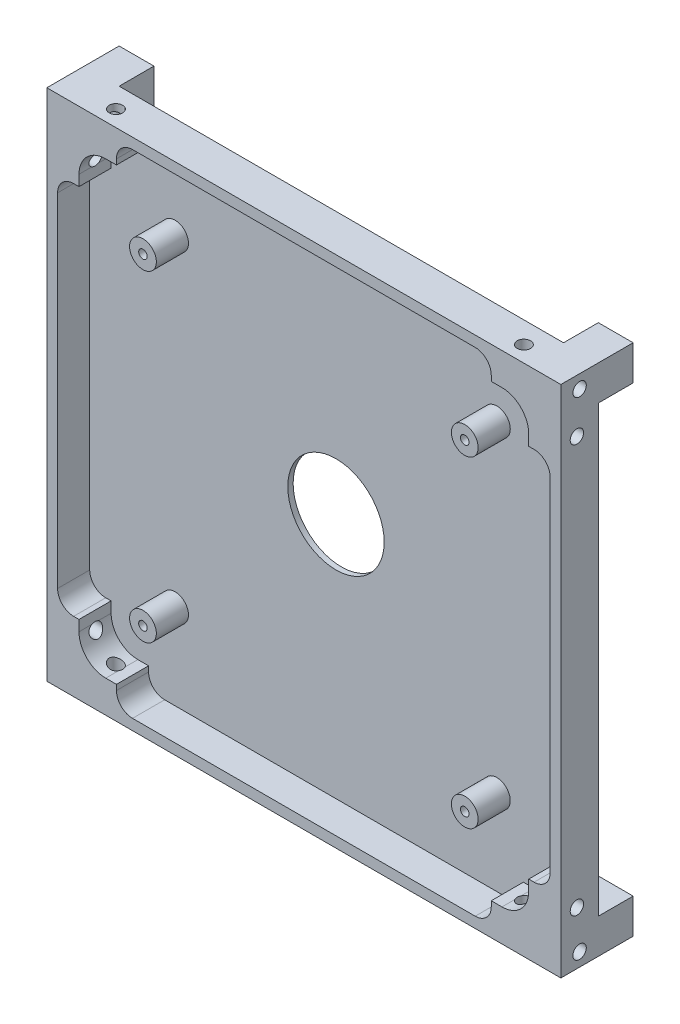
SolidWorks part; units mm, degrees
material "7075-T6 (SN)"
ref_plane "Front Plane" through (0, 0, 0) normal (0, 0, 1) x (1, 0, 0)
ref_plane "Top Plane" through (0, 0, 0) normal (0, 1, 0) x (1, 0, 0)
ref_plane "Right Plane" through (0, 0, 0) normal (1, 0, 0) x (0, 0, -1)
sketch "Sketch1" plane through (0, 0, 0) normal (0, 0, 1) x (1, 0, 0)
  line L1 (48, -48) -> (-48, -48)
  line L2 (48, -48) -> (48, 48)
  line L3 (48, 48) -> (-48, 48)
  line L4 (-48, -48) -> (-48, 48)
  line L5 (48, -48) -> (-48, 48) construction
  line L6 (48, 48) -> (-48, -48) construction
  point P0 (0, 0)
  dimension "D1" = 96
  dimension "D2" = 96
extrude "Boss-Extrude1" add sketch "Sketch1" along normal blind 2
sketch "Sketch2" plane through (0, 0, 2) normal (0, 0, 1) x (1, 0, 0)
  line L0 (48, 48) -> (-48, 48) construction
  line L1 (37, -42) -> (-37, -42)
  line L2 (42, -37) -> (42, 37)
  line L3 (37, 42) -> (-37, 42)
  line L4 (-42, -37) -> (-42, 37)
  line L5 (42, -42) -> (-42, 42) construction
  line L6 (42, 42) -> (-42, -42) construction
  line L7 (48, -48) -> (48, 48) construction
  line L12 (-48, 48) -> (-48, -48)
  line L13 (-48, -48) -> (48, -48)
  line L14 (48, -48) -> (48, 48)
  line L15 (48, 48) -> (-48, 48)
  line L16 (-48, 48) -> (-48, -48)
  line L17 (-48, -48) -> (48, -48)
  line L18 (48, -48) -> (48, 48)
  line L19 (48, 48) -> (-48, 48)
  arc A0 (-37, -42) -> (-42, -37) centre (-37, -37) cw
  arc A1 (37, -42) -> (42, -37) centre (37, -37) ccw
  arc A2 (42, 37) -> (37, 42) centre (37, 37) ccw
  arc A3 (-37, 42) -> (-42, 37) centre (-37, 37) ccw
  point P0 (0, 0)
  dimension "D4" = 5
  dimension "D1" = 6
  dimension "D2" = 6
extrude "Boss-Extrude2" add sketch "Sketch2" along normal blind 5
sketch "Sketch4" plane through (0, 0, 7) normal (0, 0, 1) x (1, 0, 0)
  line L0 (-41.5, 41.5) -> (41.5, -41.5) construction
  line L1 (-41.5, 41.5) -> (41.5, 41.5)
  line L2 (-41.5, 41.5) -> (-41.5, -41.5)
  line L3 (-41.5, -41.5) -> (41.5, -41.5)
  line L4 (41.5, 41.5) -> (41.5, -41.5)
  point P4 (0, 0)
  dimension "D1" = 83
  dimension "D2" = 83
sketch "Sketch3" plane through (0, 0, 0) normal (0, 0, -1) x (-1, 0, 0)
  line L1 (-48, 48) -> (-41.5, 48)
  line L2 (-48, 48) -> (-48, 41.5)
  line L3 (-48, 41.5) -> (-41.5, 41.5)
  line L4 (-41.5, 48) -> (-41.5, 41.5)
  line L5 (48, 48) -> (41.5, 48)
  line L6 (48, 48) -> (48, 41.5)
  line L7 (48, 41.5) -> (41.5, 41.5)
  line L8 (41.5, 48) -> (41.5, 41.5)
  line L9 (-48, -48) -> (-41.5, -48)
  line L10 (-48, -48) -> (-48, -41.5)
  line L11 (-48, -41.5) -> (-41.5, -41.5)
  line L12 (-41.5, -48) -> (-41.5, -41.5)
  line L13 (48, -48) -> (41.5, -48)
  line L14 (48, -48) -> (48, -41.5)
  line L15 (48, -41.5) -> (41.5, -41.5)
  line L16 (41.5, -48) -> (41.5, -41.5)
  dimension "D1" = 6.5
  dimension "D2" = 6.5
  dimension "D3" = 6.5
  dimension "D4" = 6.5
extrude "Boss-Extrude3" add sketch "Sketch3" along normal blind 6.5
sketch "Sketch5" plane through (0, 0, 0) normal (0, 0, -1) x (-1, 0, 0)
  circle A0 centre (0, 0) radius 9
  dimension "D1" = 18
extrude "Cut-Extrude1" cut sketch "Sketch5" against normal blind 10
sketch "Sketch6" plane through (-48, 0, 0) normal (-1, 0, 0) x (0, 0, 1)
  line L0 (-6.5, -45.5) -> (7, -45.5) construction
  line L2 (7, 48) -> (7, -48) construction
  line L3 (-6.5, 45.5) -> (7, 45.5) construction
  line L5 (7, 48) -> (-6.5, 48) construction
  line L6 (7, -48) -> (-6.5, -48) construction
  point P6 (3.5, -45.5)
  point P11 (3.5, 45.5)
  dimension "D1" = 3.5
  dimension "D2" = 3.5
  dimension "D3" = 2.5
  dimension "D4" = 2.5
hole_wizard "M3 Tapped Hole1" positions "3DSketch1" profile "Sketch7" tap size "M3" standard "ISO"
sketch3d "3DSketch1"
  point P0 (-48, 45.5, 3.5)
  point P3 (-48, -45.5, 3.5)
sketch "Sketch7" plane through (-48, 45.5, 3.5) normal (0, 1, 0) x (0, 0, 1)
  line L0 (0, 0) -> (0, 10.2511)
  line L1 (0, 10.2511) -> (1.25, 9.5)
  line L2 (1.25, 9.5) -> (1.25, 0)
  line L5 (1.25, 0) -> (0, 0)
  line L10 (0, 10.2511) -> (-1.25, 9.5) construction
  line L11 (0, -6.35) -> (0, 107.95) construction
  dimension "Tap Drill Dia." = 2.5
  dimension "Tap Drill Depth" = 9.5
  dimension "Drill Angle" = 118
cosmetic thread "Hole Thread1" parameters "D1"=8, "D2"=3
cosmetic thread "Hole Thread2" parameters "D1"=8, "D2"=3
mirror "Mirror1" about plane through (0, 0, 0) normal (1, 0, 0) of "M3 Tapped Hole1"
sketch "Sketch8" plane through (48, 0, 0) normal (1, 0, 0) x (0, 0, -1)
  point P0 (-4, -38.0996)
  point P1 (-4, 38.1004)
hole_wizard "M3 Tapped Hole2" positions "3DSketch2" profile "Sketch10" tap size "M3" standard "ISO"
sketch3d "3DSketch2"
  point P0 (48, 38.1004, 4)
  point P3 (48, -38.0996, 4)
sketch "Sketch10" plane through (48, 38.1004, 4) normal (0, 1, 0) x (0, 0, -1)
  line L0 (0, 0) -> (0, 9.2511)
  line L1 (0, 9.2511) -> (1.25, 8.5)
  line L2 (1.25, 8.5) -> (1.25, 0)
  line L5 (1.25, 0) -> (0, 0)
  line L10 (0, 9.2511) -> (-1.25, 8.5) construction
  line L11 (0, -6.35) -> (0, 107.95) construction
  dimension "Tap Drill Dia." = 2.5
  dimension "Tap Drill Depth" = 8.5
  dimension "Drill Angle" = 118
cosmetic thread "Hole Thread3" parameters "D1"=6, "D2"=3
cosmetic thread "Hole Thread4" parameters "D1"=6, "D2"=3
ref_axis "Axis1" through (0, 0, 2) along (0, 0, -1)
pattern_circular "CirPattern1" count 4 every 90 about axis through (0, 0, 2) along (0, 0, -1) of "M3 Tapped Hole2"
sketch "Sketch11" plane through (0, 0, 7) normal (0, 0, 1) x (1, 0, 0)
  line L0 (-37, -42) -> (37, -42) construction
  line L1 (32, -46) -> (-32, -46)
  line L2 (35, -43) -> (35, -42)
  line L3 (35, -42) -> (-35, -42)
  line L4 (-35, -43) -> (-35, -42)
  line L5 (-48, -48) -> (48, -48) construction
  line L6 (48, -48) -> (48, 48) construction
  line L7 (-48, 48) -> (-48, -48) construction
  line L8 (48, 48) -> (-48, 48) construction
  line L9 (-42, -35) -> (-43, -35)
  line L10 (-42, -35) -> (-42, 35)
  line L11 (-42, 35) -> (-43, 35)
  line L12 (-37, -42) -> (37, -42)
  line L13 (42, -37) -> (42, 37)
  line L14 (37, 42) -> (-37, 42)
  line L15 (-42, 37) -> (-42, -37)
  line L16 (-37, -42) -> (37, -42)
  line L17 (42, -37) -> (42, 37)
  line L18 (37, 42) -> (-37, 42)
  line L19 (-42, 37) -> (-42, -37)
  line L20 (-46, -32) -> (-46, 32)
  arc A0 (-43, 35) -> (-46, 32) centre (-43, 32) ccw
  arc A1 (-43, -35) -> (-46, -32) centre (-43, -32) cw
  arc A2 (-32, -46) -> (-35, -43) centre (-32, -43) cw
  arc A3 (32, -46) -> (35, -43) centre (32, -43) ccw
  arc A4 (-42, -37) -> (-37, -42) centre (-37, -37) ccw
  arc A5 (37, -42) -> (42, -37) centre (37, -37) ccw
  arc A6 (42, 37) -> (37, 42) centre (37, 37) ccw
  arc A7 (-37, 42) -> (-42, 37) centre (-37, 37) ccw
  arc A8 (-42, -37) -> (-37, -42) centre (-37, -37) ccw
  arc A9 (37, -42) -> (42, -37) centre (37, -37) ccw
  arc A10 (42, 37) -> (37, 42) centre (37, 37) ccw
  arc A11 (-37, 42) -> (-42, 37) centre (-37, 37) ccw
  point P10 (-35, -42.5)
  line M21 (37, -42) -> (-37, -42)
  line M23 (-42, -37) -> (-42, 37)
  dimension "D1" = 2
  dimension "D8" = 3
  dimension "D2" = 13
  dimension "D3" = 13
  dimension "D5" = 13
  dimension "D6" = 13
  dimension "D7" = 2
extrude "Cut-Extrude2" cut sketch "Sketch11" against normal up to surface (5 mm away) contours A1 L9 L11 A0 L20 M23 | L1 A3 L2 L4 A2 M21 region at (0, -43.9814, 7) region at (-43.9814, 0, 7) up to face at (9, 0, 2)
pattern_circular "CirPattern2" count 2 every 180 about axis through (0, 0, 2) along (0, 0, -1) of "Cut-Extrude2"
sketch "Sketch12" plane through (0, 0, 2) normal (0, 0, 1) x (1, 0, 0)
  line L20 (-37, -42) -> (-35, -42)
  line L21 (-35, -42) -> (-35, -43)
  line L22 (-32, -46) -> (32, -46)
  line L23 (35, -43) -> (35, -42)
  line L24 (35, -42) -> (37, -42)
  line L25 (42, -37) -> (42, -35)
  line L26 (42, -35) -> (43, -35)
  line L27 (46, -32) -> (46, 32)
  line L28 (43, 35) -> (42, 35)
  line L29 (42, 35) -> (42, 37)
  line L30 (37, 42) -> (35, 42)
  line L31 (35, 42) -> (35, 43)
  line L32 (32, 46) -> (-32, 46)
  line L33 (-35, 43) -> (-35, 42)
  line L34 (-35, 42) -> (-37, 42)
  line L35 (-42, 37) -> (-42, 35)
  line L36 (-42, 35) -> (-43, 35)
  line L37 (-46, 32) -> (-46, -32)
  line L38 (-43, -35) -> (-42, -35)
  line L39 (-42, -35) -> (-42, -37)
  line L40 (-37, -42) -> (-35, -42)
  line L41 (-35, -42) -> (-35, -43)
  line L42 (-32, -46) -> (32, -46)
  line L43 (35, -43) -> (35, -42)
  line L44 (35, -42) -> (37, -42)
  line L45 (42, -37) -> (42, -35)
  line L46 (42, -35) -> (43, -35)
  line L47 (46, -32) -> (46, 32)
  line L48 (43, 35) -> (42, 35)
  line L49 (42, 35) -> (42, 37)
  line L50 (37, 42) -> (35, 42)
  line L51 (35, 42) -> (35, 43)
  line L52 (32, 46) -> (-32, 46)
  line L53 (-35, 43) -> (-35, 42)
  line L54 (-35, 42) -> (-37, 42)
  line L55 (-42, 37) -> (-42, 35)
  line L56 (-42, 35) -> (-43, 35)
  line L57 (-46, 32) -> (-46, -32)
  line L58 (-43, -35) -> (-42, -35)
  line L59 (-42, -35) -> (-42, -37)
  arc A12 (-42, -37) -> (-37, -42) centre (-37, -37) ccw
  arc A13 (-35, -43) -> (-32, -46) centre (-32, -43) ccw
  arc A14 (32, -46) -> (35, -43) centre (32, -43) ccw
  arc A15 (37, -42) -> (42, -37) centre (37, -37) ccw
  arc A16 (43, -35) -> (46, -32) centre (43, -32) ccw
  arc A17 (46, 32) -> (43, 35) centre (43, 32) ccw
  arc A18 (42, 37) -> (37, 42) centre (37, 37) ccw
  arc A19 (35, 43) -> (32, 46) centre (32, 43) ccw
  arc A20 (-32, 46) -> (-35, 43) centre (-32, 43) ccw
  arc A21 (-37, 42) -> (-42, 37) centre (-37, 37) ccw
  arc A22 (-43, 35) -> (-46, 32) centre (-43, 32) ccw
  arc A23 (-46, -32) -> (-43, -35) centre (-43, -32) ccw
  arc A24 (-42, -37) -> (-37, -42) centre (-37, -37) ccw
  arc A25 (-35, -43) -> (-32, -46) centre (-32, -43) ccw
  arc A26 (32, -46) -> (35, -43) centre (32, -43) ccw
  arc A27 (37, -42) -> (42, -37) centre (37, -37) ccw
  arc A28 (43, -35) -> (46, -32) centre (43, -32) ccw
  arc A29 (46, 32) -> (43, 35) centre (43, 32) ccw
  arc A30 (42, 37) -> (37, 42) centre (37, 37) ccw
  arc A31 (35, 43) -> (32, 46) centre (32, 43) ccw
  arc A32 (-32, 46) -> (-35, 43) centre (-32, 43) ccw
  arc A33 (-37, 42) -> (-42, 37) centre (-37, 37) ccw
  arc A34 (-43, 35) -> (-46, 32) centre (-43, 32) ccw
  arc A35 (-46, -32) -> (-43, -35) centre (-43, -32) ccw
  dimension "D1" = 0
extrude "Cut-Extrude3" cut sketch "Sketch12" against normal blind 1
sketch "Sketch13" plane through (0, 0, 7) normal (0, 0, 1) x (1, 0, 0)
  line L4 (48, 48) -> (-48, 48)
  line L5 (-48, 48) -> (-48, -48)
  line L6 (-48, -48) -> (48, -48)
  line L7 (48, -48) -> (48, 48)
  line L8 (48, 48) -> (-48, 48)
  line L9 (-48, 48) -> (-48, -48)
  line L10 (-48, -48) -> (48, -48)
  line L11 (48, -48) -> (48, 48)
  dimension "D1" = 0
extrude "Cut-Extrude4" [suppressed] cut sketch "Sketch13" against normal blind 1
sketch "Sketch14" plane through (0, 0, 0) normal (0, 0, -1) x (-1, 0, 0)
  circle A0 centre (0, 0) radius 20
  text T0 "MSSG       -      EYE-SAT" font "Impact" height 4
  dimension "D1" = 40
sketch "Sketch15" plane through (0, 0, 1) normal (0, 0, 1) x (1, 0, 0)
  line L0 (0, 0) -> (-35.5279, 35.5279) construction
  line L1 (0, 0) -> (-32.9127, -32.9127) construction
  circle A0 centre (0, 0) radius 42.5 construction
  circle A1 centre (-30.052, 30.052) radius 2.5
  point P2 (30.052, 30.052)
  point P6 (30.052, -30.052)
  point P9 (-30.052, -30.052)
  point P10 (-30.052, 30.052)
extrude "Boss-Extrude4" add sketch "Sketch15" along normal blind 6
pattern_circular "CirPattern3" count 4 over 360 about axis through (0, 0, 2) along (0, 0, -1) of "Boss-Extrude4" reverse direction yes
hole_wizard "Tap Drill for M2x0.4 Tap1" positions "3DSketch3" profile "Sketch16" hole size "M2x0.4" standard "ANSI Metric"
sketch3d "3DSketch3"
  line L3 (-30.052, 30.052, 7) -> (-30.052, 30.052, 1) construction
  point P0 (-30.052, 30.052, 7)
  point P17 (-30.052, 30.052, 7)
sketch "Sketch16" plane through (-30.052, 30.052, 7) normal (1, 0, 0) x (0, -1, 0)
  line L0 (0, 0) -> (0, 6.4797)
  line L1 (0, 6.4797) -> (0.8, 5.999)
  line L2 (0.8, 5.999) -> (0.8, 0)
  line L5 (0.8, 0) -> (0, 0)
  line L10 (0, 6.4797) -> (-0.8, 5.999) construction
  line L11 (0, -6.35) -> (0, 107.95) construction
  dimension "Hole Dia." = 1.6
  dimension "Hole Depth" = 5.999
  dimension "Drill Angle" = 118
pattern_circular "CirPattern4" count 4 over 360 about axis through (0, 0, 2) along (0, 0, -1) of "Tap Drill for M2x0.4 Tap1"
equation "\"D2@Sketch1\"=\"D1@Sketch1\""
equation "\"thickness\" = 2"
equation "\"D1@Boss-Extrude1\"=\"thickness\""
equation "\"D2@Sketch2\"=\"D1@Sketch2\""
equation "\"D2@Sketch3\"=\"D1@Sketch3\""
equation "\"D3@Sketch3\"=\"D1@Sketch3\""
equation "\"D4@Sketch3\"=\"D1@Sketch3\""
equation "\"D2@Sketch4\"=\"D1@Sketch4\""
equation "\"D2@Sketch6\"=\"D1@Sketch6\""
equation "\"D4@Sketch6\"=\"D3@Sketch6\""
equation "\"D3@Sketch11\"=\"D2@Sketch11\""
equation "\"D5@Sketch11\"=\"D2@Sketch11\""
equation "\"D6@Sketch11\"=\"D2@Sketch11\""
equation "\"D7@Sketch11\"=\"D1@Sketch11\""
